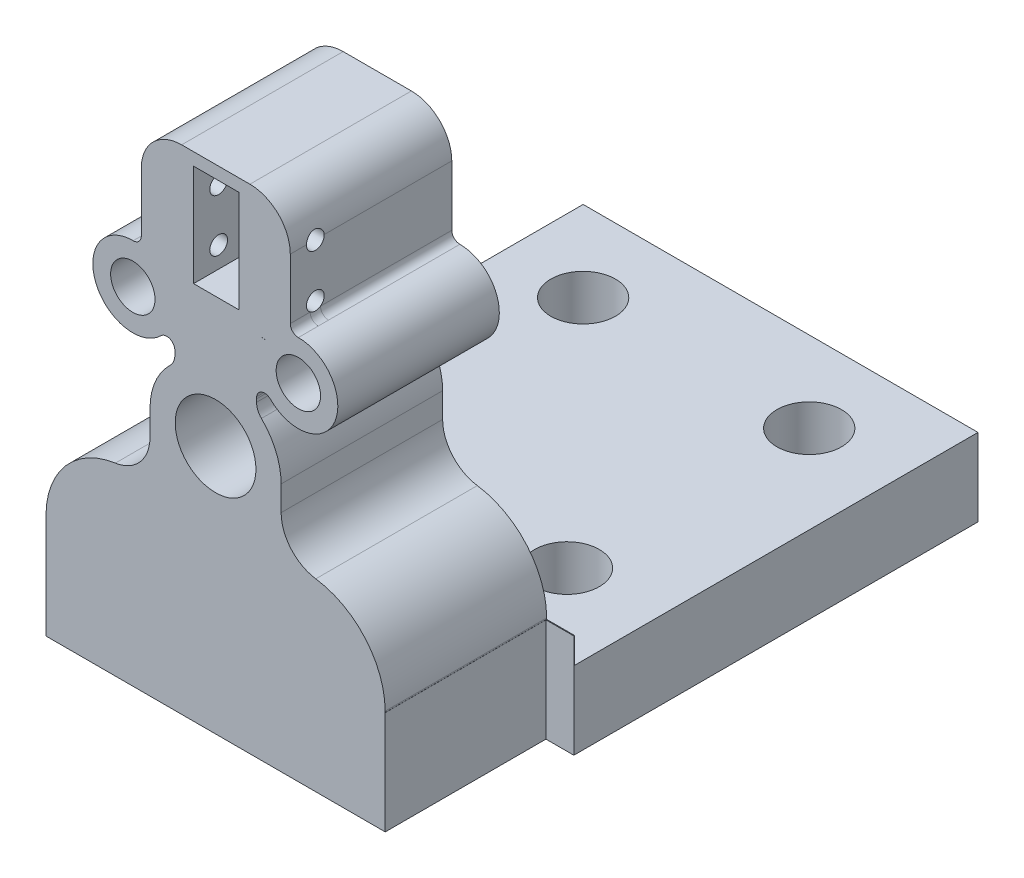
SolidWorks part; units mm, degrees
ref_plane "Alzado" through (0, 0, 0) normal (0, 0, 1) x (1, 0, 0)
ref_plane "Planta" through (0, 0, 0) normal (0, 1, 0) x (1, 0, 0)
ref_plane "Vista lateral" through (0, 0, 0) normal (1, 0, 0) x (0, 0, -1)
sketch "Croquis1" plane through (0, 0, 0) normal (0, 0, 1) x (1, 0, 0)
  line L0 (-5.0668, -5.1496) -> (-5.0668, -8.1496)
  line L1 (5.0477, -8.1756) -> (5.0477, -5.1756)
  line L2 (-8.1437, -14.5125) -> (8.0918, -14.5125) construction
  line L3 (-5.0668, -5.1496) -> (-6.0668, -5.1496)
  line L4 (-6.0259, 0) -> (-5.0259, 0)
  line L5 (6.0937, -0.0171) -> (5.0259, 0)
  line L6 (5.0477, -5.1756) -> (6.0477, -5.1756)
  line L7 (-5.0259, 0) -> (5.0259, 0)
  line L12 (-0.0259, -14.5125) -> (-0.0259, 3.7196) construction
  line L13 (10.2241, -2.6334) -> (-0.0259, -14.5125) construction
  line L14 (-0.0259, -14.5125) -> (-10.276, -2.5412) construction
  line L15 (-10.276, -2.5412) -> (-0.0259, -2.5412) construction
  line L16 (-0.0259, -2.5412) -> (10.2241, -2.6334) construction
  arc A0 (-5.0668, -8.1496) -> (5.0477, -8.1756) centre (-0.0259, -14.5125) ccw
  circle A1 centre (-0.0259, -14.5125) radius 5
  arc A2 (-6.0259, 0) -> (-6.0668, -5.1496) centre (-10.276, -2.5412) ccw
  circle A3 centre (-10.276, -2.5412) radius 2.75
  arc A4 (6.0937, -0.0171) -> (6.0477, -5.1756) centre (10.2241, -2.6334) cw
  circle A5 centre (10.2241, -2.6334) radius 2.75
  point P18 (0, 0)
  dimension "D1" = 10.2501
  dimension "D5" = 5.5
  dimension "D3" = 3
  dimension "D4" = 1
  dimension "D7" = 10.25
  dimension "D8" = 15.69
  dimension "D10" = 15.76
extrude "Saliente-Extruir1" add sketch "Croquis1" along normal blind 20
ref_plane "Plano1" through (0, 0, 10) normal (0, 0, -1) x (-1, 0, 0)
sketch "Croquis5" plane through (0, 0, 10) normal (0, 0, -1) x (-1, 0, 0)
  line L0 (0.0259, -14.5125) -> (0.0259, -32.5925) construction
  line L1 (-8.0918, -14.5125) -> (-8.0918, -32.5925)
  line L2 (-8.0918, -32.5925) -> (8.1437, -32.5925)
  line L3 (8.1437, -32.5925) -> (8.1437, -14.5125)
  arc A0 (-5.0477, -8.1756) -> (5.0668, -8.1496) centre (0.0259, -14.5125) ccw construction
  arc A1 (8.1437, -14.5125) -> (-8.0918, -14.5125) centre (0.0259, -14.5125) cw
  dimension "D1" = 18.08
extrude "Saliente-Extruir4" add sketch "Croquis5" along normal mid plane 20
sketch "Croquis7" plane through (0, 0, 20) normal (0, 0, 1) x (1, 0, 0)
  line L0 (20.9741, -32.5925) -> (-21.0259, -32.5925)
  line L2 (8.0918, -32.5925) -> (-8.1437, -32.5925) construction
  point P3 (-0.0259, -32.5925)
  point P6 (-0.0259, -32.5925)
  dimension "D1" = 42
extrude "Extruir-Lámina1" add sketch "Croquis7" against normal blind 20 thin
sketch "Croquis8" plane through (0, 0, 20) normal (0, 0, 1) x (1, 0, 0)
  line L0 (-0.0259, -14.5125) -> (-0.0259, -32.5925) construction
  line L5 (20.9741, -32.5925) -> (-21.0259, -32.5925) construction
  line L7 (-21.0259, -32.5925) -> (20.9855, -32.5925)
  line L8 (-21.0259, -32.5925) -> (-21.0259, -45.386)
  line L9 (-21.0259, -45.386) -> (20.9855, -45.386)
  line L10 (20.9855, -32.5925) -> (20.9855, -45.386)
extrude "Saliente-Extruir6" add sketch "Croquis8" against normal blind 52
fillet "Redondeo1" radius 2 4 edges at (-5.0668, -8.1496, 10) (5.0477, -8.1756, 10) (-5.0668, -5.1496, 10) (5.0477, -5.1756, 10)
fillet "Redondeo2" radius 1 2 edges at (6.0477, -5.1756, 10) (-6.0668, -5.1496, 10)
sketch "Croquis9" plane through (0, 0, 20) normal (0, 0, 1) x (1, 0, 0)
  line L1 (9.2249, 0) -> (-9.2249, 0)
  line L2 (9.2249, 0) -> (9.2249, 15.7)
  line L3 (9.2249, 15.7) -> (-9.2249, 15.7)
  line L4 (-9.2249, 0) -> (-9.2249, 15.7)
  line L5 (-9.2249, 0) -> (6.0259, 0) construction
  line L6 (0, 1.55) -> (-0.0202, -45.386) construction
  line L7 (-2.75, 14.15) -> (2.85, 14.15)
  line L8 (-2.75, 14.15) -> (-2.75, 1.55)
  line L9 (-2.75, 1.55) -> (2.85, 1.55)
  line L10 (2.85, 14.15) -> (2.85, 1.55)
  line L11 (-21.0259, -45.386) -> (20.9855, -45.386) construction
  circle A0 centre (-10.276, -2.5412) radius 2.75 construction
  point P3 (0, 0)
  point P4 (-8.9189, -0.1494)
  point P10 (0, 0)
  point P20 (0, 0)
  point P21 (0, 0)
  dimension "D1" = 15.7
  dimension "D2" = 1.55
  dimension "D3" = 12.6
  dimension "D4" = 5.6
  dimension "D5" = 6.3749
extrude "Saliente-Extruir7" add sketch "Croquis9" against normal up to vertex (13.6 mm away)
sketch "Croquis11" plane through (9.2249, 0, 0) normal (1, 0, 0) x (0, 0, -1)
  line L0 (0, 14.15) -> (-20, 14.15) construction
  circle A0 centre (-16.8993, 10.65) radius 1.1
  circle A1 centre (-16.8993, 4.15) radius 1.1
  dimension "D1" = 6.5
  dimension "D2" = 2.2
  dimension "D3" = 2.2
  dimension "D4" = 3.5
extrude "Cortar-Extruir1" cut sketch "Croquis11" against normal through all both and the other way through all
fillet "Redondeo4" radius 5 2 edges at (8.0918, -22.5925, 10) (-8.1437, -22.5925, 10)
fillet "Redondeo5" radius 10 8 edges at (17.033, -22.5925, 0) (13.0918, -22.5925, 10) (17.033, -22.5925, 20) (20.9741, -22.5925, 10) (-17.0848, -22.5925, 20) (-13.1437, -22.5925, 10) (-17.0848, -22.5925, 0) (-21.0259, -22.5925, 10)
sketch "Croquis12" plane through (0, -32.5925, 0) normal (0, 1, 0) x (1, 0, 0)
  line L0 (0, 0) -> (-0.0202, 32) construction
  line L1 (24.4399, -0.1) -> (-24.4601, -0.1)
  line L2 (24.4399, -0.1) -> (24.4399, 32.1)
  line L3 (24.4399, 32.1) -> (-24.4601, 32.1)
  line L4 (-24.4601, -0.1) -> (-24.4601, 32.1)
  line L5 (24.4399, -0.1) -> (-24.4601, 32.1) construction
  line L6 (24.4399, 32.1) -> (-24.4601, -0.1) construction
  line L7 (20.9855, 32) -> (-21.0259, 32) construction
  point P0 (-0.0101, 16)
  point P11 (-0.0101, 16)
  dimension "D1" = 48.9
  dimension "D2" = 32.2
extrude "Saliente-Extruir8" add sketch "Croquis12" against normal up to surface (12.7935 mm away) up to face at (-0.0202, -45.386, -6)
sketch "Croquis13" plane through (0, 0, -32.1) normal (0, 0, -1) x (-1, 0, 0)
  line L1 (-24.4399, -32.5925) -> (24.4601, -32.5925)
  line L2 (-24.4399, -32.5925) -> (-24.4399, -45.386)
  line L3 (-24.4399, -45.386) -> (24.4601, -45.386)
  line L4 (24.4601, -32.5925) -> (24.4601, -45.386)
extrude "Saliente-Extruir9" add sketch "Croquis13" along normal blind 17.85
sketch "Croquis14" plane through (0, -32.5925, 0) normal (0, 1, 0) x (1, 0, 0)
  line L0 (-24.4601, 49.95) -> (24.4399, 49.95) construction
  line L1 (-24.4601, 49.95) -> (-24.4601, -0.1) construction
  circle A0 centre (-14.4601, 39.95) radius 4
  circle A1 centre (13.5399, 39.95) radius 4
  circle A2 centre (13.5399, 9.95) radius 4
  circle A3 centre (-14.4601, 9.95) radius 4
  dimension "D1" = 8
  dimension "D2" = 10
  dimension "D3" = 10
  dimension "D4" = 2
  dimension "D5" = 2
extrude "Cortar-Extruir2" cut sketch "Croquis14" against normal blind 17.85
fillet "Redondeo6" radius 1 2 edges at (9.2249, 2.1527, 10) (-9.2249, 2.2978, 10)
fillet "Redondeo7" radius 5 2 edges at (-9.2249, 15.7, 10) (9.2249, 15.7, 10)
sketch "Croquis16" plane through (0, 0, 20) normal (0, 0, 1) x (1, 0, 0)
  point P6 (0, 0)
sketch "Croquis17" plane through (24.4399, 0, 0) normal (1, 0, 0) x (0, 0, -1)
  line L0 (-0.1, -45.386) -> (95, -45.386) construction
  line L1 (95, -45.386) -> (95, -35.786) construction
  line L4 (95, -35.786) -> (0, -35.786)
  line L5 (95, -35.786) -> (95, -22.5424)
  line L6 (95, -22.5424) -> (0, -22.5424)
  line L7 (0, -35.786) -> (0, -22.5424)
  dimension "D1" = 95.1
  dimension "D2" = 9.6
extrude "Cortar-Extruir10" cut sketch "Croquis17" against normal through all
sketch "Croquis18" plane through (24.4399, 0, 0) normal (1, 0, 0) x (0, 0, -1)
  line L0 (-0.1, -45.386) -> (-0.1, -35.786) construction
  line L1 (-0.1, -32.5925) -> (-0.1, -45.386) construction
  line L2 (-0.1, -35.786) -> (95, -35.786) construction
  line L3 (95, -35.786) -> (95, -45.386) construction
  line L12 (95, -45.386) -> (-0.1, -45.386) construction
  line L14 (95, -35.786) -> (49.95, -35.786)
  line L15 (95, -35.786) -> (95, -45.386)
  line L16 (95, -45.386) -> (49.95, -45.386)
  line L17 (49.95, -35.786) -> (49.95, -45.386)
  dimension "D1" = 9.6
  dimension "D2" = 95.1
